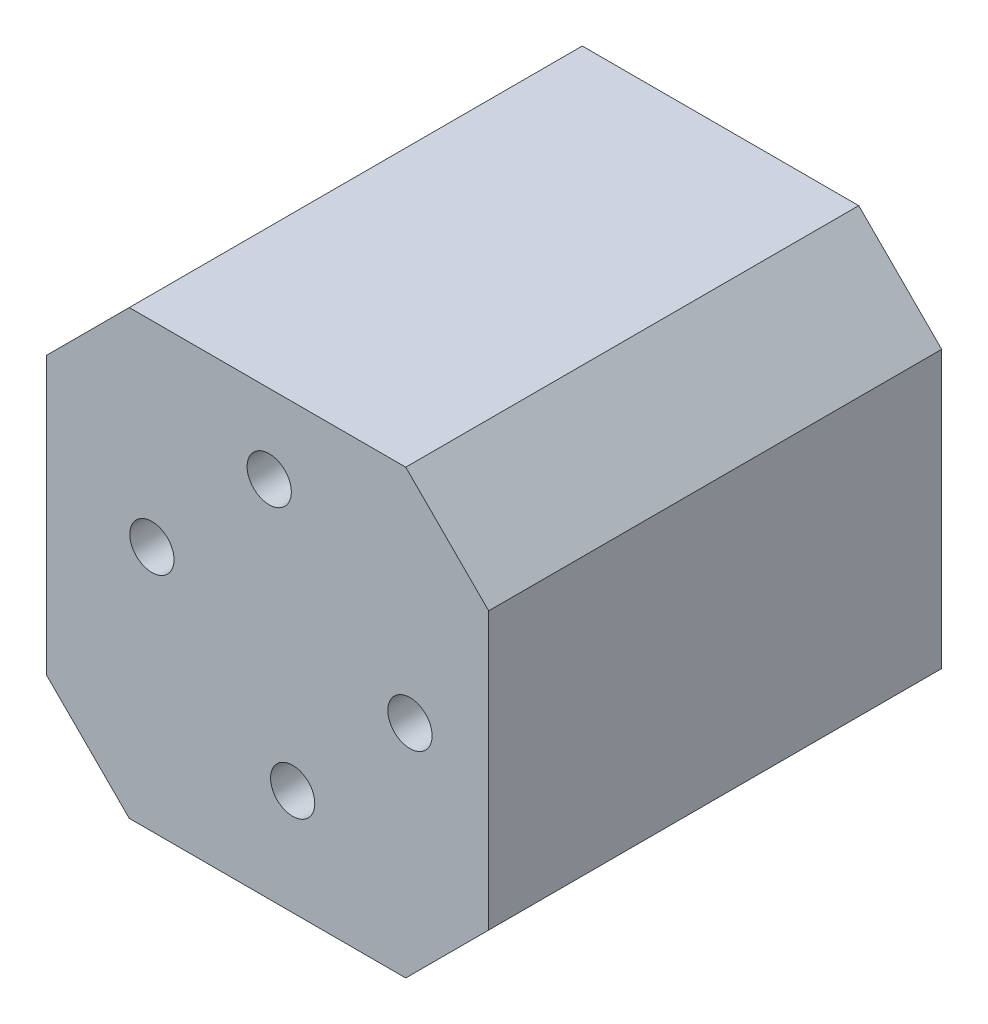
SolidWorks part; units mm, degrees
ref_plane "Front Plane" through (0, 0, 0) normal (0, 0, 1) x (1, 0, 0)
ref_plane "Top Plane" through (0, 0, 0) normal (0, 1, 0) x (1, 0, 0)
ref_plane "Right Plane" through (0, 0, 0) normal (1, 0, 0) x (0, 0, -1)
sketch "Sketch1" plane through (0, 0, 0) normal (0, 0, 1) x (1, 0, 0)
  line L0 (7.5, 40) -> (0, 32.5)
  line L1 (7.5, 0) -> (32.5, 0)
  line L2 (0, 7.5) -> (0, 32.5)
  line L3 (7.5, 40) -> (32.5, 40)
  line L4 (40, 7.5) -> (40, 32.5)
  line L5 (0, 7.5) -> (7.5, 0)
  line L6 (32.5, 40) -> (40, 32.5)
  line L7 (40, 7.5) -> (32.5, 0)
  line L8 (7.5, 0) -> (0, 0) construction
  line L9 (0, 0) -> (0, 7.5) construction
  dimension "D1" = 40
  dimension "D2" = 40
  dimension "D3" = 25
  dimension "D4" = 32.5
extrude "Boss-Extrude1" add sketch "Sketch1" along normal blind 40.96
sketch "Sketch2" plane through (0, 0, 40.96) normal (0, 0, 1) x (1, 0, 0)
  line L0 (7.5, 40) -> (0, 32.5) construction
  line L1 (20.1544, 32.8823) -> (9.5478, 22.2756) construction
  line L2 (9.5478, 22.2756) -> (22.2757, 9.5477) construction
  line L3 (22.2757, 9.5477) -> (32.8823, 20.1543) construction
  line L4 (32.8823, 20.1543) -> (20.1544, 32.8823) construction
  line L5 (32.5, 40) -> (7.5, 40) construction
  circle A0 centre (20.1544, 32.8823) radius 2
  circle A1 centre (9.5478, 22.2756) radius 2
  circle A2 centre (22.2757, 9.5477) radius 2
  circle A3 centre (32.8823, 20.1543) radius 2
  dimension "D2" = 4
  dimension "D1" = 7.1177
  dimension "D3" = 13.981
  dimension "D4" = 15
  dimension "D5" = 18
extrude "Cut-Extrude1" cut sketch "Sketch2" against normal through all
